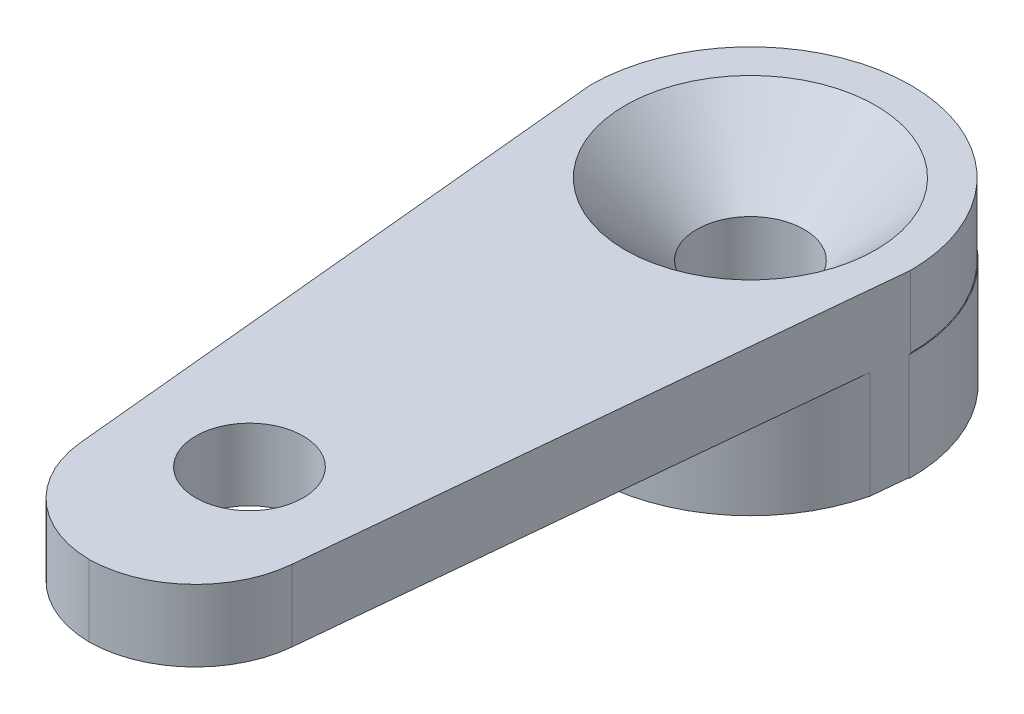
SolidWorks part; units mm, degrees
material "PBT General Purpose"
ref_plane "Front Plane" through (0, 0, 0) normal (0, 0, 1) x (1, 0, 0)
ref_plane "Top Plane" through (0, 0, 0) normal (0, 1, 0) x (1, 0, 0)
ref_plane "Right Plane" through (0, 0, 0) normal (1, 0, 0) x (0, 0, -1)
sketch "Sketch1" plane through (0, 0, 0) normal (0, 1, 0) x (1, 0, 0)
  circle A0 centre (0, 0) radius 4.5
  dimension "D1" = 9
extrude "Boss-Extrude1" add sketch "Sketch1" along normal blind 3
sketch "Sketch2" plane through (0, 3, 0) normal (0, 1, 0) x (1, 0, 0)
  line L0 (0, 0) -> (0, -14) construction
  line L1 (4.4797, 0) -> (4.4797, -14)
  line L2 (-4.4797, 0) -> (-4.4797, -14)
  arc A0 (4.4797, 0) -> (-4.4797, 0) centre (0, 0) ccw
  arc A1 (-4.4797, -14) -> (4.4797, -14) centre (0, -14) ccw
  point P3 (0, -7)
  dimension "D1" = 14
extrude "Boss-Extrude2" add sketch "Sketch2" along normal blind 2
sketch "Sketch3" plane through (0, 5, 0) normal (0, 1, 0) x (1, 0, 0)
  circle A0 centre (0, -14) radius 1
  dimension "D1" = 2
extrude "Cut-Extrude1" cut sketch "Sketch3" against normal blind 2
sketch "Sketch4" plane through (0, 5, 0) normal (0, 1, 0) x (1, 0, 0)
  circle A0 centre (0, 0) radius 1.5
  dimension "D1" = 3
extrude "Cut-Extrude3" cut sketch "Sketch4" against normal blind 32
chamfer "Chamfer1" distance 2 angle 45 1 edges at (0, 5, 1.5)
sketch "Sketch5" plane through (0, 5, 0) normal (0, 1, 0) x (1, 0, 0)
  line L0 (4.4797, 0) -> (2.7815, -17.5115)
  line L1 (-4.4797, 0) -> (-2.7815, -17.5115)
  line L2 (-4.4797, 0) -> (-11.9702, -15.3202)
  line L3 (-11.9702, -15.3202) -> (-2.7815, -17.5115)
  line L4 (4.4797, 0) -> (7.8238, -10.6485)
  line L5 (7.8238, -10.6485) -> (5.76, -17.1401)
  line L6 (5.76, -17.1401) -> (2.7815, -17.5115)
  arc A0 (-4.4797, -14) -> (4.4797, -14) centre (0, -14) ccw construction
extrude "Cut-Extrude4" cut sketch "Sketch5" against normal blind 32
fillet "Fillet1" radius 3 2 edges at (-2.7815, 4, 17.5115) (2.7815, 4, 17.5115)
sketch "Sketch6" plane through (0, 5, 0) normal (0, 1, 0) x (1, 0, 0)
  circle A0 centre (0, -14) radius 1.5
  dimension "D1" = 3
extrude "Cut-Extrude5" cut sketch "Sketch6" against normal blind 2
